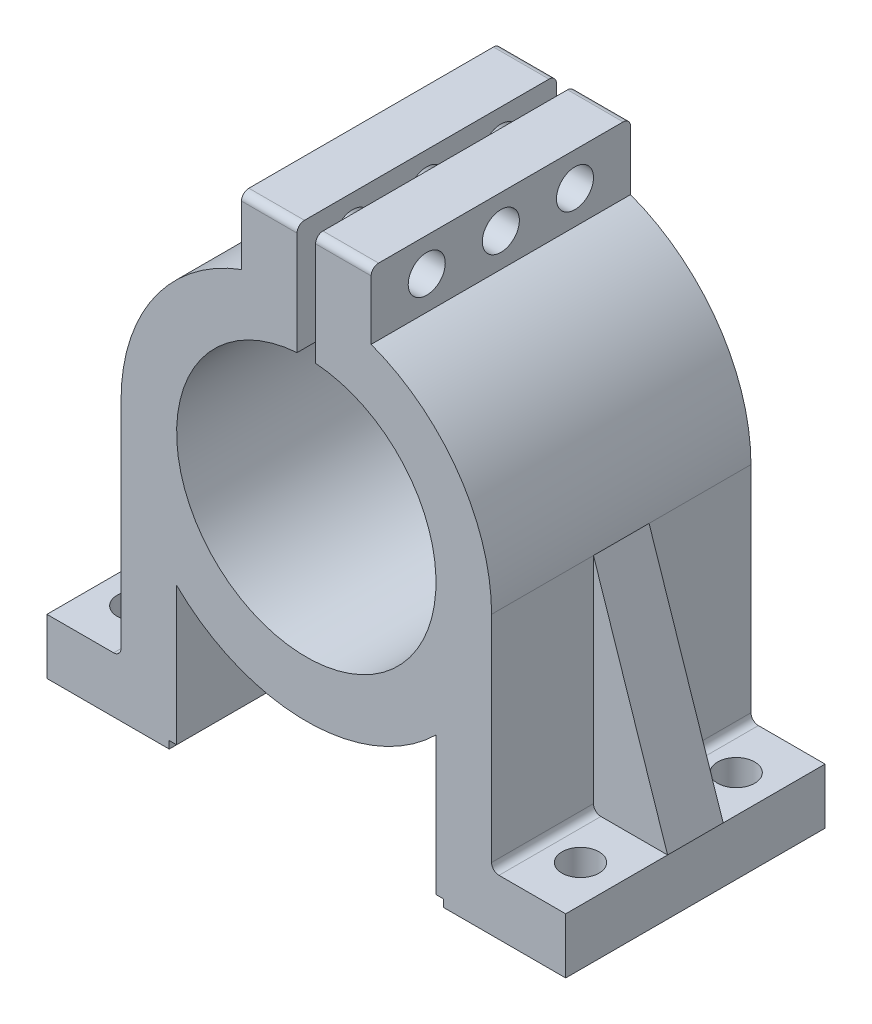
SolidWorks part; units mm, degrees
ref_plane "Alzado" through (0, 0, 0) normal (0, 0, 1) x (1, 0, 0)
ref_plane "Planta" through (0, 0, 0) normal (0, 1, 0) x (1, 0, 0)
ref_plane "Vista lateral" through (0, 0, 0) normal (1, 0, 0) x (0, 0, -1)
sketch "Croquis2" plane through (0, 0, 0) normal (0, 0, 1) x (1, 0, 0)
  line L0 (-10, 0) -> (-10, -11.6)
  line L1 (-10.4, -12) -> (-14, -12)
  line L2 (-14, -12) -> (-14, -15)
  line L3 (-14, -15) -> (-7.4, -15)
  line L4 (-7, -14.6) -> (-7, -7.1414)
  line L5 (0, 0) -> (0, -2.8073) construction
  line L6 (7, -14.6) -> (7, -7.1414)
  line L7 (14, -15) -> (7.4, -15)
  line L8 (14, -12) -> (14, -15)
  line L9 (10.4, -12) -> (14, -12)
  line L10 (10, 0) -> (10, -11.6)
  line L11 (-7, -14.6) -> (-7.4, -14.6)
  line L12 (-7.4, -14.6) -> (-7.4, -15)
  line L13 (7, -14.6) -> (7.4, -14.6)
  line L14 (7.4, -14.6) -> (7.4, -15)
  line L15 (0.5, 12.9675) -> (0.5, 9.9875)
  line L16 (0.5, 12.9675) -> (3.5, 12.9675)
  line L17 (3.5, 12.9675) -> (3.5, 9.3675)
  line L18 (0.5, 9.9875) -> (0.5, 6.9821)
  line L19 (-3.5, 12.9675) -> (-3.5, 9.3675)
  line L20 (-0.5, 12.9675) -> (-3.5, 12.9675)
  line L21 (-0.5, 12.9675) -> (-0.5, 9.9875)
  line L22 (-0.5, 9.9875) -> (-0.5, 6.9821)
  arc A0 (-0.5, 6.9821) -> (0.5, 6.9821) centre (0, 0) ccw
  arc A1 (-3.5, 9.3675) -> (-10, 0) centre (0, 0) ccw
  arc A2 (-7, -7.1414) -> (7, -7.1414) centre (0, 0) ccw
  arc A3 (10, 0) -> (3.5, 9.3675) centre (0, 0) ccw
  arc A4 (-10, -11.6) -> (-10.4, -12) centre (-10.4, -11.6) cw
  arc A5 (10.4, -12) -> (10, -11.6) centre (10.4, -11.6) cw
  point P32 (-10, -12)
  point P35 (10, -12)
  dimension "D1" = 14
  dimension "D2" = 20
  dimension "D13" = 0.4
  dimension "D14" = 0.4
  dimension "D3" = 12
  dimension "D4" = 3
  dimension "D5" = 7
  dimension "D6" = 4
  dimension "D7" = 0.4
  dimension "D8" = 0.4
  dimension "D9" = 6.6
  dimension "D10" = 0.5
  dimension "D11" = 3
  dimension "D12" = 3.6
extrude "Saliente-Extruir1" add sketch "Croquis2" along normal blind 7 and the other way blind 7
fillet "Redondeo1" radius 0.4 4 edges at (-2, 12.9675, 7) (-2, 12.9675, -7) (2, 12.9675, -7) (2, 12.9675, 7)
sketch "Croquis3" plane through (0, 0, 0) normal (0, 0, 1) x (1, 0, 0)
  line L0 (10, 0) -> (14, -12)
  line L1 (10, 0) -> (10, -12)
  line L2 (10, -12) -> (14, -12)
  line L3 (0, 0) -> (0, 3.4414) construction
  line L4 (-10, -12) -> (-14, -12)
  line L5 (-10, 0) -> (-10, -12)
  line L6 (-10, 0) -> (-14, -12)
extrude "Saliente-Extruir2" add sketch "Croquis3" along normal blind 1.5 and the other way blind 1.5
sketch "Croquis4" plane through (0, -12, 0) normal (0, 1, 0) x (1, 0, 0)
  line L0 (14, -7) -> (10.4, -7) construction
  line L1 (14, -1.5) -> (14, -7) construction
  line L2 (0, 0) -> (4.1363, 0) construction
  line L3 (0, 0) -> (0, 2.5972) construction
  circle A0 centre (12, -4.2) radius 1
  circle A1 centre (12, 4.2) radius 1
  circle A2 centre (-12, 4.2) radius 1
  circle A3 centre (-12, -4.2) radius 1
  dimension "D1" = 2
  dimension "D2" = 2.8
  dimension "D3" = 2
extrude "Cortar-Extruir1" cut sketch "Croquis4" against normal up to next
sketch "Croquis5" plane through (3.5, 0, 0) normal (1, 0, 0) x (0, 0, -1)
  line L0 (6.6, 12.9675) -> (-6.6, 12.9675) construction
  circle A0 centre (0, 11.1675) radius 1
  circle A1 centre (4, 11.1675) radius 1
  circle A2 centre (-4, 11.1675) radius 1
  dimension "D1" = 2
  dimension "D2" = 1.8
  dimension "D3" = 2
  dimension "D4" = 2
extrude "Cortar-Extruir2" cut sketch "Croquis5" against normal blind 8.5
